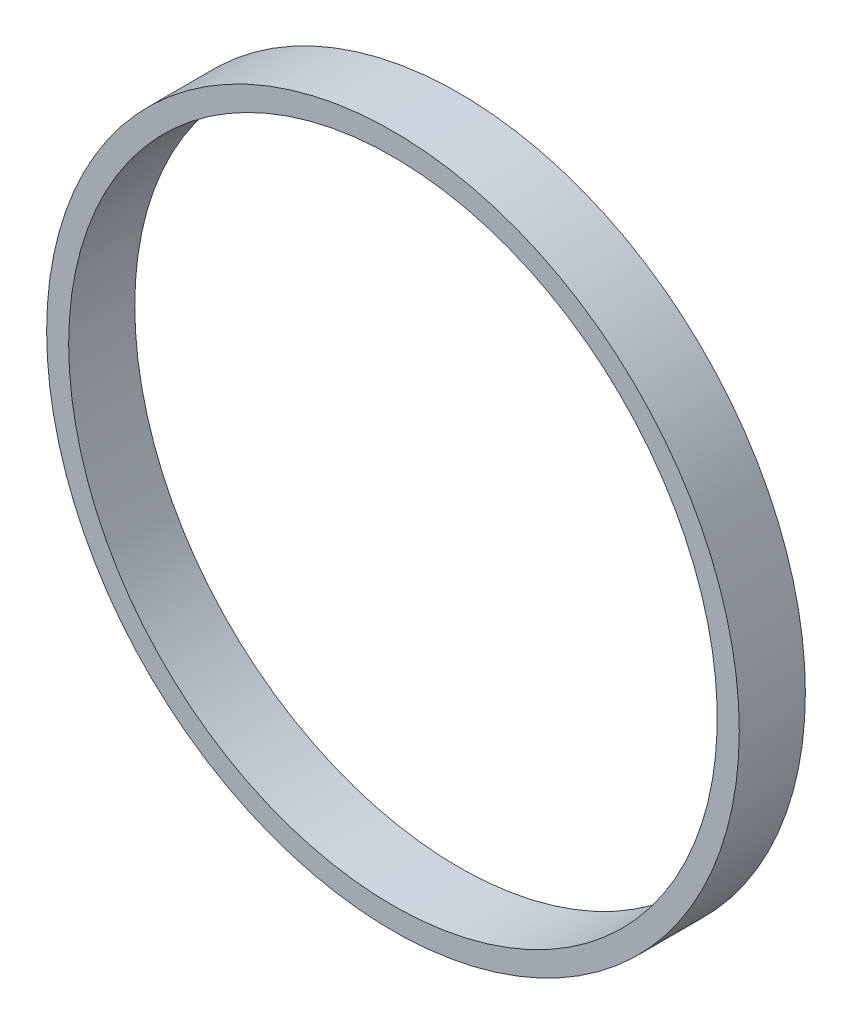
SolidWorks part; units mm, degrees
material "Acrylic (Medium-high impact)"
ref_plane "Front Plane" through (0, 0, 0) normal (0, 0, 1) x (1, 0, 0)
ref_plane "Top Plane" through (0, 0, 0) normal (0, 1, 0) x (1, 0, 0)
ref_plane "Right Plane" through (0, 0, 0) normal (1, 0, 0) x (0, 0, -1)
sketch "Sketch1" plane through (0, 0, 0) normal (0, 0, 1) x (1, 0, 0)
  circle A0 centre (0, 0) radius 24.9555
  circle A1 centre (0, 0) radius 24.9555 construction
  circle A2 centre (0, 0) radius 23.368
  dimension "D1" = 1.5875
extrude "Boss-Extrude1" add sketch "Sketch1" along normal blind 4.7625
